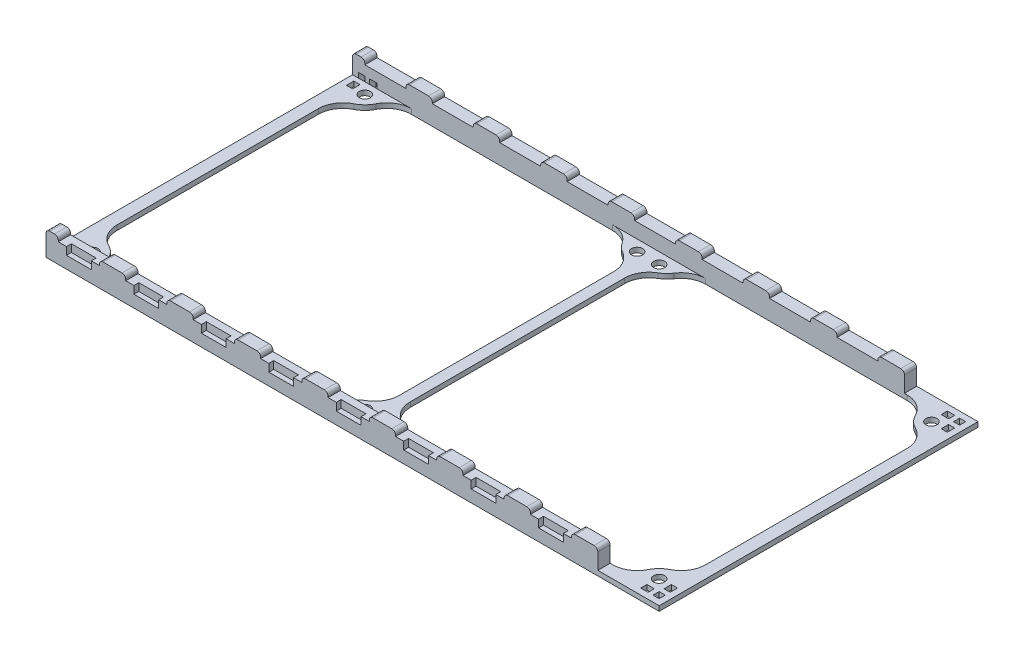
SolidWorks part; units mm, degrees
ref_plane "Front Plane" through (0, 0, 0) normal (0, 0, 1) x (1, 0, 0)
ref_plane "Top Plane" through (0, 0, 0) normal (0, 1, 0) x (1, 0, 0)
ref_plane "Right Plane" through (0, 0, 0) normal (1, 0, 0) x (0, 0, -1)
sketch "Sketch1" plane through (0, 0, 0) normal (0, 1, 0) x (1, 0, 0)
  line L1 (0, 0) -> (250, 0)
  line L2 (0, 0) -> (0, 130)
  line L3 (0, 130) -> (250, 130)
  line L4 (250, 0) -> (250, 130)
  line L5 (5, 5) -> (245, 5)
  line L6 (5, 5) -> (5, 125)
  line L7 (5, 125) -> (245, 125)
  line L8 (245, 5) -> (245, 125)
  dimension "D1" = 250
  dimension "D2" = 130
  dimension "D3" = 240
  dimension "D4" = 120
  dimension "D5" = 5
  dimension "D6" = 5
extrude "Boss-Extrude1" add sketch "Sketch1" along normal blind 2
sketch "Sketch2" plane through (0, 0, 0) normal (0, 1, 0) x (1, 0, 0)
  line L0 (245, 125) -> (5, 125) construction
  line L1 (5, 5) -> (14, 5)
  line L2 (5, 5) -> (5, 14)
  line L3 (5, 14) -> (14, 14)
  line L4 (14, 5) -> (14, 14)
  line L5 (5, 125) -> (14, 125)
  line L6 (5, 125) -> (5, 116)
  line L7 (5, 116) -> (14, 116)
  line L8 (14, 125) -> (14, 116)
  line L9 (116, 125) -> (125, 125)
  line L10 (116, 125) -> (116, 116)
  line L11 (116, 116) -> (125, 116)
  line L14 (5, 5) -> (245, 5) construction
  line L15 (125, 116) -> (134, 116)
  line L17 (125, 125) -> (134, 125)
  line L18 (134, 116) -> (134, 125)
  line L19 (116, 5) -> (134, 5)
  line L20 (116, 5) -> (116, 14)
  line L21 (116, 14) -> (134, 14)
  line L22 (134, 5) -> (134, 14)
  line L24 (245, 125) -> (236, 125)
  line L25 (245, 125) -> (245, 116)
  line L26 (245, 116) -> (236, 116)
  line L27 (236, 125) -> (236, 116)
  line L28 (245, 5) -> (236, 5)
  line L29 (245, 5) -> (245, 14)
  line L30 (245, 14) -> (236, 14)
  line L31 (236, 5) -> (236, 14)
  circle A0 centre (9.5, 9.5) radius 2.25
  circle A1 centre (9.5, 120.5) radius 2.25
  circle A2 centre (120.5, 120.5) radius 2.25
  circle A3 centre (129.5, 120.5) radius 2.25
  circle A4 centre (120.5, 9.5) radius 2.25
  circle A5 centre (129.5, 9.5) radius 2.25
  circle A6 centre (240.5, 120.5) radius 2.25
  circle A7 centre (240.5, 9.5) radius 2.25
  dimension "D9" = 4.5
  dimension "D10" = 4.5
  dimension "D12" = 4.5
  dimension "D18" = 4.5
  dimension "D16" = 4.5
  dimension "D23" = 4.5
  dimension "D27" = 4.5
  dimension "D32" = 4.5
  dimension "D2" = 4.5
  dimension "D3" = 4.5
  dimension "D4" = 4.5
  dimension "D5" = 4.5
  dimension "D6" = 4.5
  dimension "D7" = 4.5
  dimension "D8" = 4.5
  dimension "D11" = 4.5
  dimension "D13" = 4.5
  dimension "D14" = 4.5
  dimension "D15" = 4.5
  dimension "D17" = 4.5
  dimension "D19" = 4.5
  dimension "D20" = 4.5
  dimension "D21" = 4.5
  dimension "D22" = 4.5
  dimension "D24" = 9
  dimension "D25" = 4.5
  dimension "D26" = 120
  dimension "D28" = 4.5
  dimension "D29" = 4.5
  dimension "D30" = 4.5
  dimension "D31" = 4.5
  dimension "D33" = 4.5
  dimension "D34" = 4.5
  dimension "D35" = 4.5
  dimension "D36" = 4.5
extrude "Boss-Extrude2" add sketch "Sketch2" along normal blind 2
fillet "Fillet1" radius 10 12 edges at (5, 1, -14) (14, 1, -5) (5, 1, -116) (14, 1, -125) (116, 1, -125) (134, 1, -125) (245, 1, -116) (236, 1, -125) (245, 1, -14) (236, 1, -5) (116, 1, -5) (134, 1, -5)
fillet "Fillet2" radius 10 8 edges at (14, 1, -14) (116, 1, -14) (134, 1, -14) (236, 1, -14) (236, 1, -116) (134, 1, -116) (116, 1, -116) (14, 1, -116)
sketch "Sketch3" plane through (0, 0, 0) normal (0, 1, 0) x (1, 0, 0)
  line L1 (122.7534, 116) -> (127.2466, 116)
  line L2 (122.7534, 116) -> (122.7534, 14)
  line L3 (122.7534, 14) -> (127.2466, 14)
  line L4 (127.2466, 116) -> (127.2466, 14)
extrude "Boss-Extrude3" add sketch "Sketch3" along normal blind 2
fillet "Fillet3" radius 10 4 edges at (122.7534, 1, -116) (127.2466, 1, -116) (127.2466, 1, -14) (122.7534, 1, -14)
sketch "Sketch4" plane through (0, 2, 0) normal (0, 1, 0) x (1, 0, 0)
  line L1 (5, 0) -> (21.8, 0)
  line L2 (5, 0) -> (5, 5)
  line L3 (5, 5) -> (21.8, 5)
  line L4 (21.8, 0) -> (21.8, 5)
  line L5 (5, 130) -> (21.7, 130)
  line L6 (5, 130) -> (5, 125)
  line L7 (5, 125) -> (21.7, 125)
  line L8 (21.7, 130) -> (21.7, 125)
  dimension "D1" = 16.8
  dimension "D2" = 5
  dimension "D3" = 5
  dimension "D4" = 16.7
extrude "Boss-Extrude4" add sketch "Sketch4" along normal blind 6
sketch "Sketch5" plane through (0, 2, 0) normal (0, 1, 0) x (1, 0, 0)
  line L0 (106.0501, 125) -> (23.9499, 125) construction
  line L1 (21.7, 130) -> (32.5, 130)
  line L2 (21.7, 130) -> (21.7, 125)
  line L3 (21.7, 125) -> (32.5, 125)
  line L4 (32.5, 130) -> (32.5, 125)
  line L5 (5, 130) -> (5, 125) construction
  line L6 (21.8, 0) -> (250, 0) construction
  line L7 (21.8, 5) -> (32.5, 5)
  line L8 (21.8, 5) -> (21.8, 0)
  line L9 (21.8, 0) -> (32.5, 0)
  line L10 (32.5, 5) -> (32.5, 0)
  line L11 (5, 5) -> (5, 0) construction
  dimension "D1" = 27.5
  dimension "D2" = 27.5
extrude "Boss-Extrude5" add sketch "Sketch5" along normal blind 8
fillet "Fillet4" radius 1.5 4 edges at (21.8, 10, -2.5) (32.5, 10, -2.5) (32.5, 10, -127.5) (21.7, 10, -127.5)
sketch "Sketch6" plane through (0, 2, 0) normal (0, 1, 0) x (1, 0, 0)
  line L1 (0, 130) -> (5, 130)
  line L2 (0, 130) -> (0, 125)
  line L3 (0, 125) -> (5, 125)
  line L4 (5, 130) -> (5, 125)
  line L5 (0, 0) -> (5, 0)
  line L6 (0, 0) -> (0, 5)
  line L7 (0, 5) -> (5, 5)
  line L8 (5, 0) -> (5, 5)
extrude "Boss-Extrude6" add sketch "Sketch6" along normal blind 8
sketch "Sketch10" plane through (0, 0, 0) normal (0, 0, 1) x (1, 0, 0)
  line L0 (5, 8) -> (21.8, 8) construction
  line L1 (8.35, 8) -> (18.45, 8)
  line L2 (8.35, 8) -> (8.35, 4.9)
  line L3 (8.35, 4.9) -> (18.45, 4.9)
  line L4 (18.45, 8) -> (18.45, 4.9)
  line L6 (5, 10) -> (5, 8) construction
  dimension "D1" = 10.1
  dimension "D2" = 3.1
  dimension "D3" = 3.35
extrude "Cut-Extrude2" cut sketch "Sketch10" against normal blind 2
pattern_linear "LPattern1" count 8 spacing 27.5 along (1, 0, 0) of "Boss-Extrude4", "Boss-Extrude5", "Fillet4"
fillet "Fillet5" radius 1.5 4 edges at (0, 10, -127.5) (5, 10, -127.5) (0, 10, -2.5) (5, 10, -2.5)
sketch "Sketch9" plane through (0, 0, 0) normal (0, 1, 0) x (1, 0, 0)
  line L0 (3.5, 0) -> (5, 0) construction
  line L1 (5, 5) -> (2.5, 5)
  line L2 (5, 5) -> (5, 2.5)
  line L3 (5, 2.5) -> (2.5, 2.5)
  line L4 (2.5, 5) -> (2.5, 2.5)
  line L5 (0, 0) -> (0, 5) construction
  line L6 (23.9499, 5) -> (0, 5) construction
  line L7 (10, 5) -> (7, 5)
  line L8 (10, 5) -> (10, 2.5)
  line L9 (10, 2.5) -> (7, 2.5)
  line L10 (7, 5) -> (7, 2.5)
  line L11 (1.5, 0) -> (3.5, 0) construction
  line L12 (5, 10) -> (2.5, 10)
  line L13 (5, 10) -> (5, 7)
  line L14 (5, 7) -> (2.5, 7)
  line L15 (2.5, 10) -> (2.5, 7)
  dimension "D1" = 2.5
  dimension "D2" = 2.5
  dimension "D3" = 2.5
  dimension "D4" = 2.5
  dimension "D5" = 3
  dimension "D6" = 2.5
  dimension "D7" = 10
  dimension "D8" = 3
  dimension "D9" = 10
extrude "Cut-Extrude1" cut sketch "Sketch9" along normal blind 4
ref_plane "Plane1" through (125, 0, 0) normal (-1, 0, 0) x (0, 0, 1)
ref_plane "Plane2" through (0, 0, -65) normal (0, 0, 1) x (1, 0, 0)
mirror "Mirror1" about plane through (0, 0, -65) normal (0, 0, 1) of "Cut-Extrude1" second plane through (125, 0, 0) second plane normal (-1, 0, 0)
pattern_linear "LPattern2" count 8 spacing 27.5 along (1, 0, 0) of "Cut-Extrude2"
